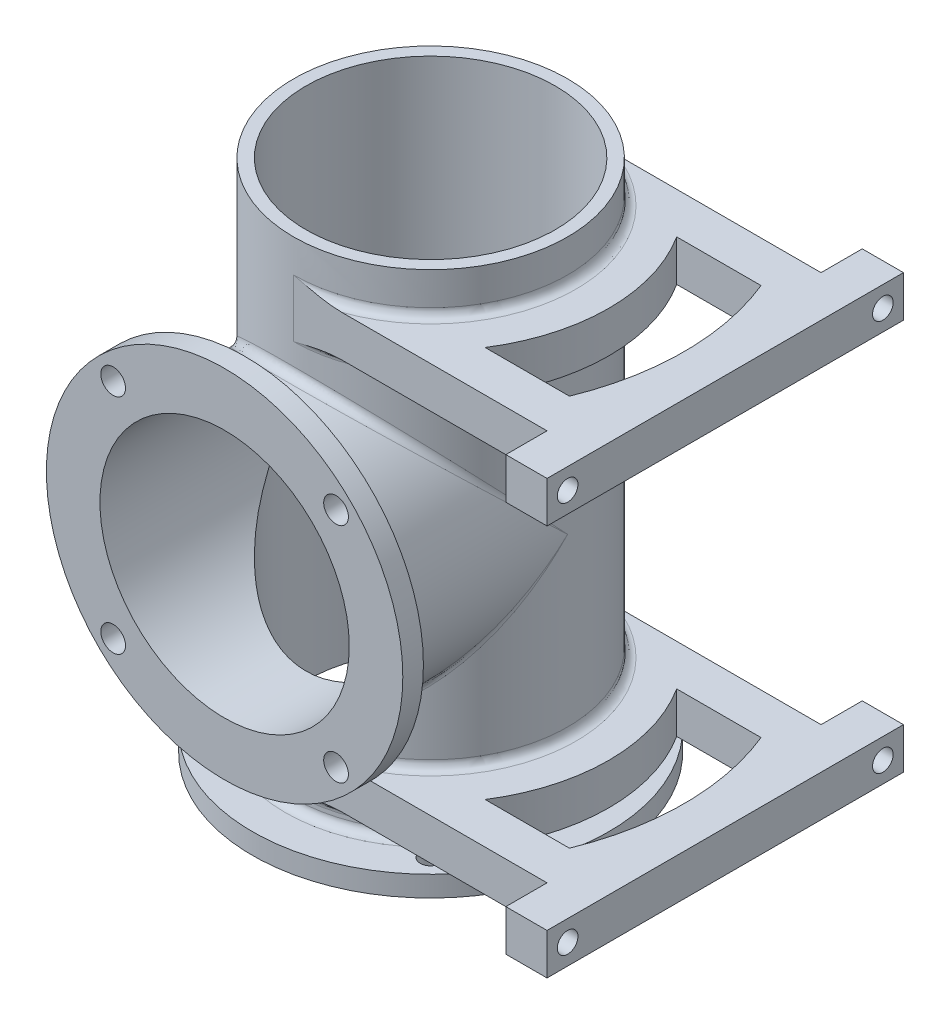
SolidWorks part; units mm, degrees
ref_plane "Front Plane" through (0, 0, 0) normal (0, 0, 1) x (1, 0, 0)
ref_plane "Top Plane" through (0, 0, 0) normal (0, 1, 0) x (1, 0, 0)
ref_plane "Right Plane" through (0, 0, 0) normal (1, 0, 0) x (0, 0, -1)
sketch "Sketch1" plane through (0, 0, 0) normal (0, 1, 0) x (1, 0, 0)
  circle A0 centre (0, 0) radius 30.25 construction
  circle A1 centre (0, 0) radius 33.25
  dimension "D1" = 60.5
  dimension "D2" = 3
extrude "Boss-Extrude1" add sketch "Sketch1" along normal blind 125 contours A1
sketch "Sketch2" plane through (0, 0, 0) normal (0, 0, 1) x (1, 0, 0)
  line L0 (33.25, 125) -> (-33.25, 125) construction
  circle A0 centre (0, 62.5) radius 33.25
  dimension "D1" = 66.5
  dimension "D2" = 62.5
extrude "Boss-Extrude2" add sketch "Sketch2" along normal blind 45
sketch "Sketch3" plane through (0, 0, 0) normal (0, -1, 0) x (-1, 0, 0)
  circle A0 centre (0, 0) radius 43.25
  circle A1 centre (0, 0) radius 33.25 construction
  dimension "D1" = 10
extrude "Boss-Extrude3" add sketch "Sketch3" against normal blind 5
sketch "Sketch4" plane through (0, 0, 45) normal (0, 0, 1) x (1, 0, 0)
  circle A0 centre (0, 62.5) radius 43.25
  circle A1 centre (0, 62.5) radius 33.25 construction
  dimension "D1" = 10
extrude "Boss-Extrude4" add sketch "Sketch4" along normal blind 5
sketch "Sketch9" plane through (0, 0, 0) normal (1, 0, 0) x (0, 0, -1)
  line L0 (0, 0) -> (0, 125) construction
  line L1 (33.25, 125) -> (-33.25, 125) construction
  line L2 (-33.25, 125) -> (-33.25, 95.75) construction
  line L3 (33.25, 115) -> (-33.25, 115)
  line L4 (33.25, 115) -> (33.25, 105)
  line L5 (33.25, 105) -> (-33.25, 105)
  line L6 (-33.25, 115) -> (-33.25, 105)
  line L7 (33.25, 115) -> (-33.25, 105) construction
  line L8 (33.25, 105) -> (-33.25, 115) construction
  line L9 (43.25, 5) -> (-43.25, 5) construction
  line L10 (33.25, 10) -> (-33.25, 10)
  line L11 (33.25, 10) -> (33.25, 20)
  line L12 (33.25, 20) -> (-33.25, 20)
  line L13 (-33.25, 10) -> (-33.25, 20)
  line L14 (33.25, 10) -> (-33.25, 20) construction
  line L15 (33.25, 20) -> (-33.25, 10) construction
  point P5 (0, 110)
  point P12 (0, 15)
  dimension "D1" = 10
  dimension "D2" = 10
  dimension "D3" = 10
  dimension "D4" = 5
extrude "Boss-Extrude5" add sketch "Sketch9" along normal blind 71.5
sketch "Sketch10" plane through (71.5, 0, 0) normal (1, 0, 0) x (0, 0, -1)
  line L0 (0, 115) -> (0, 105) construction
  line L1 (33.25, 115) -> (-33.25, 115) construction
  line L2 (-33.25, 105) -> (33.25, 105) construction
  line L3 (33.25, 20) -> (-33.25, 20) construction
  line L7 (-43.25, 115) -> (43.25, 115)
  line L8 (-43.25, 115) -> (-43.25, 105)
  line L9 (-43.25, 105) -> (43.25, 105)
  line L10 (43.25, 115) -> (43.25, 105)
  line L11 (-43.25, 115) -> (43.25, 105) construction
  line L12 (-43.25, 105) -> (43.25, 115) construction
  line L17 (-43.25, 10) -> (43.25, 10)
  line L18 (-43.25, 10) -> (-43.25, 20)
  line L19 (-33.25, 115) -> (-33.25, 105) construction
  line L20 (-43.25, 20) -> (43.25, 20)
  line L21 (43.25, 10) -> (43.25, 20)
  line L22 (-43.25, 10) -> (43.25, 20) construction
  line L23 (-43.25, 20) -> (43.25, 10) construction
  line L24 (33.25, 10) -> (33.25, 20) construction
  line L25 (-33.25, 20) -> (-33.25, 10) construction
  point P6 (0, 15)
  point P12 (0, 110)
  dimension "D1" = 10
  dimension "D2" = 0
  dimension "D3" = 10
  dimension "D4" = 10
  dimension "D5" = 10
  dimension "D6" = 10
extrude "Boss-Extrude6" add sketch "Sketch10" against normal blind 10
sketch "Sketch11" plane through (0, 115, 0) normal (0, 1, 0) x (1, 0, 0)
  line L0 (56.9358, 23.25) -> (36.4692, 23.25)
  line L1 (56.9358, -23.25) -> (36.4692, -23.25)
  line L2 (61.5, -33.25) -> (0, -33.25) construction
  line L3 (61.5, 33.25) -> (0, 33.25) construction
  arc A0 (36.4692, -23.25) -> (36.4692, 23.25) centre (0, 0) ccw
  arc A1 (56.9358, -23.25) -> (56.9358, 23.25) centre (0, 0) ccw
  dimension "D1" = 10
  dimension "D2" = 10
extrude "Cut-Extrude5" cut sketch "Sketch11" against normal blind 170
sketch "Sketch5" plane through (0, 0, 0) normal (0, -1, 0) x (-1, 0, 0)
  line L0 (0, 0) -> (0, -38.25) construction
  line L1 (0, 0) -> (-27.0468, -27.0468)
  line L2 (0, 0) -> (-27.0468, 27.0468)
  line L3 (0, 0) -> (27.0468, 27.0468)
  line L4 (0, 0) -> (27.0468, -27.0468)
  circle A0 centre (0, 0) radius 38.25 construction
  circle A1 centre (0, 0) radius 43.25 construction
  circle A6 centre (27.0468, -27.0468) radius 2.5
  circle A7 centre (-27.0468, -27.0468) radius 2.5
  circle A8 centre (-27.0468, 27.0468) radius 2.5
  circle A9 centre (27.0468, 27.0468) radius 2.5
  dimension "D1" = 5
  dimension "D6" = 5
  dimension "D7" = 5
  dimension "D8" = 5
  dimension "D9" = 5
  dimension "D2" = 45
  dimension "D3" = 90
  dimension "D4" = 90
  dimension "D5" = 90
extrude "Cut-Extrude1" cut sketch "Sketch5" against normal blind 5 contours A6 | A7 | A8 | A9 region at (24.8025, 0, 26.1172) region at (29.2912, 0, -27.9765) region at (-26.1172, 0, -29.2912) region at (-27.9765, 0, 24.8025)
sketch "Sketch6" plane through (0, 0, 0) normal (0, -1, 0) x (-1, 0, 0)
  circle A0 centre (0, 0) radius 30.25
  dimension "D1" = 60.5
extrude "Cut-Extrude2" cut sketch "Sketch6" against normal through all
sketch "Sketch7" plane through (0, 0, 50) normal (0, 0, 1) x (1, 0, 0)
  circle A0 centre (0, 62.5) radius 30.25
  dimension "D1" = 60.5
extrude "Cut-Extrude3" cut sketch "Sketch7" against normal blind 50
sketch "Sketch8" plane through (0, 0, 50) normal (0, 0, 1) x (1, 0, 0)
  line L0 (0, 62.5) -> (0, 100.75) construction
  line L1 (0, 62.5) -> (27.0468, 89.5468)
  line L2 (0, 62.5) -> (27.0468, 35.4532)
  line L3 (0, 62.5) -> (-27.0468, 35.4532)
  line L4 (0, 62.5) -> (-27.0468, 89.5468)
  circle A0 centre (0, 62.5) radius 38.25 construction
  circle A1 centre (0, 62.5) radius 43.25 construction
  circle A2 centre (-27.0468, 89.5468) radius 3
  circle A3 centre (27.0468, 89.5468) radius 3
  circle A4 centre (27.0468, 35.4532) radius 3
  circle A5 centre (-27.0468, 35.4532) radius 3
  dimension "D1" = 5
  dimension "D6" = 6
  dimension "D7" = 6
  dimension "D8" = 6
  dimension "D9" = 6
  dimension "D2" = 45
  dimension "D3" = 90
  dimension "D4" = 90
  dimension "D5" = 90
extrude "Cut-Extrude4" cut sketch "Sketch8" against normal up to next contours A3 | A4 | A5 | A2 region at (25.9313, 92.2401, 50) region at (28.1624, 38.1464, 50) region at (-24.3536, 36.5687, 50)
sketch "Sketch12" plane through (61.5, 0, 0) normal (-1, 0, 0) x (0, 0, 1)
  line L0 (-43.25, 110) -> (43.25, 110) construction
  line L1 (-43.25, 105) -> (-43.25, 115) construction
  line L2 (43.25, 115) -> (43.25, 105) construction
  line L3 (38.25, 115) -> (38.25, 110) construction
  line L4 (33.25, 115) -> (43.25, 115) construction
  line L5 (43.25, 10) -> (33.25, 10) construction
  line L6 (43.25, 15) -> (-43.25, 15) construction
  line L7 (43.25, 20) -> (43.25, 10) construction
  line L8 (-43.25, 10) -> (-43.25, 20) construction
  line L9 (-38.25, 115) -> (-38.25, 110) construction
  line L10 (-43.25, 115) -> (-33.25, 115) construction
  line L11 (-33.25, 10) -> (-43.25, 10) construction
  line L12 (-38.25, 15) -> (-38.25, 10) construction
  line L13 (38.25, 15) -> (38.25, 10) construction
  circle A0 centre (-38.25, 110) radius 2.5
  circle A1 centre (38.25, 110) radius 2.5
  circle A2 centre (38.25, 15) radius 2.5
  circle A3 centre (-38.25, 15) radius 2.5
  dimension "D1" = 5
  dimension "D2" = 5
  dimension "D3" = 5
  dimension "D4" = 5
extrude "Cut-Extrude6" cut sketch "Sketch12" against normal through all
sketch "Sketch13" plane through (61.5, 0, 0) normal (-1, 0, 0) x (0, 0, 1)
  circle A0 centre (-38.25, 110) radius 4
  circle A1 centre (38.25, 110) radius 4
  circle A2 centre (38.25, 15) radius 4
  circle A3 centre (-38.25, 15) radius 4
  dimension "D1" = 8
  dimension "D2" = 8
  dimension "D3" = 8
  dimension "D4" = 8
extrude "Cut-Extrude7" cut sketch "Sketch13" against normal blind 4
fillet "Fillet1" radius 2 4 edges at (33.25, 10, 0) (33.25, 20, 0) (33.25, 105, 0) (33.25, 115, 0)
fillet "Fillet2" radius 2 4 edges at (33.25, 62.5, 45) (0, 5, -33.25) (0, 95.75, 33.25) (0, 29.25, 33.25)
